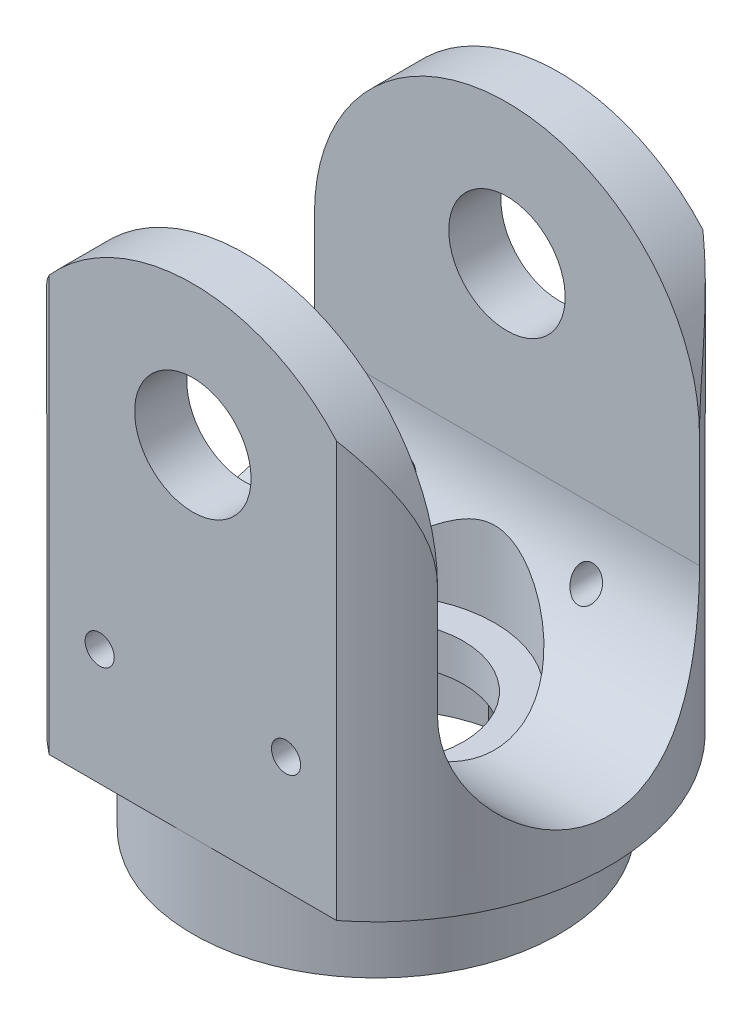
SolidWorks part; units mm, degrees
material "7075-T6 (SN)"
ref_plane "X-Y Datum" through (0, 0, 0) normal (0, 0, 1) x (1, 0, 0)
ref_plane "X-Z Datum" through (0, 0, 0) normal (0, 1, 0) x (1, 0, 0)
ref_plane "Y-Z Datum" through (0, 0, 0) normal (1, 0, 0) x (0, 0, -1)
sketch "Sketch1" plane through (0, 0, 0) normal (0, 1, 0) x (1, 0, 0)
  circle A0 centre (0, 0) radius 12.7
  dimension "D1" = 25.4
extrude "Boss-Extrude1" add sketch "Sketch1" along normal blind 15.367 and the other way blind 15.367
ref_plane "Plane2" through (0, 0, 9.9886) normal (0, 0, 1) x (1, 0, 0)
sketch "Sketch4" plane through (0, 0, 9.9886) normal (0, 0, 1) x (1, 0, 0)
  line L1 (-12.7, 15.367) -> (12.7, 15.367)
  line L2 (-12.7, 15.367) -> (-12.7, -15.367)
  line L3 (-12.7, -15.367) -> (12.7, -15.367)
  line L4 (12.7, 15.367) -> (12.7, -15.367)
extrude "Cut-Extrude2" cut sketch "Sketch4" along normal through all
mirror "Mirror2" about plane through (0, 0, 0) normal (0, 0, 1) of "Cut-Extrude2"
sketch "Sketch5" plane through (0, 0, 0) normal (1, 0, 0) x (0, 0, -1)
  line L0 (9.9886, 15.367) -> (-9.9886, 15.367) construction
  line L1 (-7.1437, 15.367) -> (7.1437, 15.367)
  line L2 (-7.1437, 15.367) -> (-7.1437, -1.27)
  line L3 (-7.1437, -1.27) -> (7.1438, -1.27)
  line L4 (7.1437, 15.367) -> (7.1438, -1.27)
  line L5 (0, 13.97) -> (0, -13.97) construction
  line L6 (0, -8.4138) -> (0, 15.367) construction
  arc A0 (-7.1437, -1.27) -> (7.1438, -1.27) centre (0, -1.27) ccw
  dimension "D3" = 16.637
  dimension "D4" = 23.7808
  dimension "D1" = 14.2875
  dimension "D2" = 7.1437
extrude "Cut-Extrude3" cut sketch "Sketch5" against normal through all both and the other way through all contours L6 A0 L3 | A0 L6 L3 | L2 L1 L4 L3 region at (0, -4.3019, 3.0319) region at (0, -4.3019, -3.0319)
sketch "Sketch6" plane through (0, 0, 9.9886) normal (0, 0, 1) x (1, 0, 0)
  line L0 (0, -43.0151) -> (0, 43.0151) construction
  line L1 (-7.8434, 15.367) -> (7.8434, 15.367) construction
  line L2 (10.5004, 4.8666) -> (14.8497, 4.8666)
  line L3 (-10.5004, 4.8666) -> (-14.8497, 4.8666)
  circle A0 centre (0, 4.8666) radius 10.5004
  arc A1 (14.8497, 4.8666) -> (-14.8497, 4.8666) centre (0, 4.8666) ccw
  line M2 (7.8434, 15.367) -> (-7.8434, 15.367)
  line M3 (-7.8434, 15.367) -> (-7.8434, -15.367)
  line M5 (7.8434, -15.367) -> (7.8434, 15.367)
  dimension "D1" = 21.0007
extrude "Cut-Extrude4" cut sketch "Sketch6" against normal through all contours L2 A1 L3 A0 M3 M2 M5 | A0 M2 M3 | A0 M5 M2 region at (10.124, 8.7197, 9.9886) region at (5.9543, 14.3505, 9.9886) region at (-5.9543, 14.3505, 9.9886)
sketch "Sketch7" plane through (0, -15.367, 0) normal (0, -1, 0) x (1, 0, 0)
  circle A0 centre (0, 0) radius 4.7625
  dimension "D1" = 9.525
extrude "Cut-Extrude5" cut sketch "Sketch7" against normal through all
sketch "Sketch9" plane through (0, -15.367, 0) normal (0, -1, 0) x (1, 0, 0)
  circle A0 centre (0, 0) radius 9.9822
  circle A1 centre (0, 0) radius 17.8528
  dimension "D1" = 19.9644
extrude "Cut-Extrude6" cut sketch "Sketch9" against normal blind 4.572
ref_plane "Plane3" through (0, 15.367, 0) normal (0, 1, 0) x (1, 0, 0)
sketch "Sketch10" plane through (0, 15.367, 0) normal (0, 1, 0) x (1, 0, 0)
  circle A0 centre (0, 0) radius 6.477
  dimension "D1" = 12.954
extrude "Cut-Extrude7" cut sketch "Sketch10" against normal blind 24.257
sketch "Sketch11" plane through (0, 0, 9.9886) normal (0, 0, 1) x (1, 0, 0)
  line L0 (-9.9822, -10.795) -> (9.9822, -10.795) construction
  line L1 (0, 7.747) -> (0, 0) construction
  circle A0 centre (0, 7.747) radius 3.175
  dimension "D1" = 6.35
  dimension "D2" = 18.542
extrude "Cut-Extrude8" cut sketch "Sketch11" against normal through all
sketch "Sketch12" plane through (0, 0, -9.9886) normal (0, 0, -1) x (-1, 0, 0)
  line L0 (-7.8434, -10.795) -> (7.8434, -10.795) construction
  line L1 (7.8434, 11.848) -> (7.8434, -10.795) construction
  line L2 (-7.8434, -10.795) -> (-7.8434, 11.848) construction
  circle A0 centre (5.0811, -4.445) radius 0.7938
  circle A1 centre (-5.0811, -4.445) radius 0.7938
  point P6 (-5.8749, -4.445)
  point P7 (5.8749, -4.445)
  dimension "D1" = 1.5875
  dimension "D2" = 1.5875
  dimension "D3" = 6.35
  dimension "D4" = 6.35
  dimension "D5" = 1.9685
  dimension "D6" = 1.9685
extrude "Cut-Extrude9" cut sketch "Sketch12" against normal through all both and the other way through all
sketch "Sketch13" plane through (0, -15.367, 0) normal (0, -1, 0) x (1, 0, 0)
  line L0 (-0.2399, -7.9974) -> (7.5971, -2.5099)
  line L1 (4.5892, -6.554) -> (0, 0) construction
  line L2 (-2.54, 0) -> (2.54, 0)
  circle A0 centre (0, 0) radius 8.001
  circle M5 centre (0, 0) radius 4.7625
  dimension "D1" = 16.002
  dimension "D2" = 35
  dimension "D3" = 6.4135
  dimension "D4" = 5.08
extrude "Cut-Extrude10" [suppressed] cut sketch "Sketch13" against normal blind 4.445 contours L0 A0 M5
sketch "Sketch14" [suppressed] plane through (0, -15.367, 0) normal (0, -1, 0) x (1, 0, 0)
  line L0 (0, 0) -> (-0.2399, -7.9974) construction
  line L1 (0, 0) -> (7.5971, -2.5099) construction
  circle A0 centre (-0.217, -7.2354) radius 1.5875
  circle A1 centre (6.8736, -2.2708) radius 1.5875
  dimension "D1" = 3.175
  dimension "D2" = 3.175
  dimension "D3" = 0.762
  dimension "D4" = 0.762
extrude "Cut-Extrude11" [suppressed] cut sketch "Sketch14" against normal up to surface (4.445 mm away) up to face at (0, -15.367, -4.7625)
sketch "Sketch15" plane through (0, -15.367, 0) normal (0, -1, 0) x (1, 0, 0)
  line L0 (-0.2399, -7.9974) -> (7.5971, -2.5099)
  line L1 (4.5892, -6.554) -> (0, 0) construction
  line L2 (-1.905, 0) -> (1.905, 0)
  circle A1 centre (0, 0) radius 9.9822 construction
  circle A2 centre (0, 0) radius 8.001
  circle M4 centre (0, 0) radius 4.7625
  dimension "D3" = 16.002
  dimension "D1" = 35
  dimension "D2" = 6.4135
  dimension "D4" = 3.81
extrude "Cut-Extrude12" cut sketch "Sketch15" against normal blind 4.445 contours A2 M4 region at (-5.4145, -15.367, 5.5794)
sketch "Sketch16" plane through (0, -15.367, 0) normal (0, -1, 0) x (1, 0, 0)
  line L0 (0, 0) -> (-0.2399, -7.9974) construction
  line L1 (0, 0) -> (7.5971, -2.5099) construction
  circle A4 centre (-0.217, -7.2354) radius 1.5875
  circle A5 centre (6.8736, -2.2708) radius 1.5875
  dimension "D1" = 3.175
  dimension "D4" = 0.762
  dimension "D2" = 3.175
  dimension "D3" = 0.762
extrude "Cut-Extrude13" cut sketch "Sketch16" against normal up to surface (4.445 mm away) up to face at (0, -10.922, -4.7625)
sketch "Pick Up Point" plane through (0, 0, 0) normal (0, 0, 1) x (1, 0, 0)
  point P0 (0, 7.747)
ref_plane "Plane4" through (0, 15.367, -7.1437) normal (0, 1, 0) x (1, 0, 0)
sketch "Sketch20" plane through (0, 15.367, -7.1437) normal (0, 1, 0) x (1, 0, 0)
  circle A0 centre (0, -7.1437) radius 12.7
  point P3 (0, 5.5562)
  point P4 (0, -19.8438)
  point P6 (0, -7.1437)
  dimension "D1" = 25.4
ref_plane "Plane5" through (0, -15.367, 0) normal (0, -1, 0) x (-1, 0, 0)
sketch "Sketch21" plane through (0, -15.367, 0) normal (0, -1, 0) x (-1, 0, 0)
  point P0 (0, 0)
ref_point "Point1"
ref_point "Point2"
ref_point "Point3"
ref_point "Point4"
ref_point "Point5"
ref_axis "Axis1" [suppressed] through (0, -8.89, 0) along (0, -1, 0)
sketch "Sketch22" plane through (0, 0, 9.9886) normal (0, 0, 1) x (1, 0, 0)
  arc A0 (7.8434, 11.848) -> (-7.8434, 11.848) centre (0, 4.8666) ccw construction
  point P0 (0, 15.367)
sketch "Sketch23" plane through (0, -10.922, 0) normal (0, -1, 0) x (1, 0, 0)
  line L0 (-1.693, -7.8198) -> (7.9273, -1.0834)
  arc A0 (7.9273, -1.0834) -> (-1.693, -7.8198) centre (0, 0) ccw
sketch3d "3DSketch1"
  line L0 (0, 7.747, 9.9886) -> (0, 7.747, -9.9886) construction
  line L3 (0, 7.747, 7.1437) -> (0, 7.747, 9.9886) construction
  line L4 (0, 7.747, -9.9886) -> (0, 7.747, -7.1438) construction
  point P6 (0, 7.747, 0)
